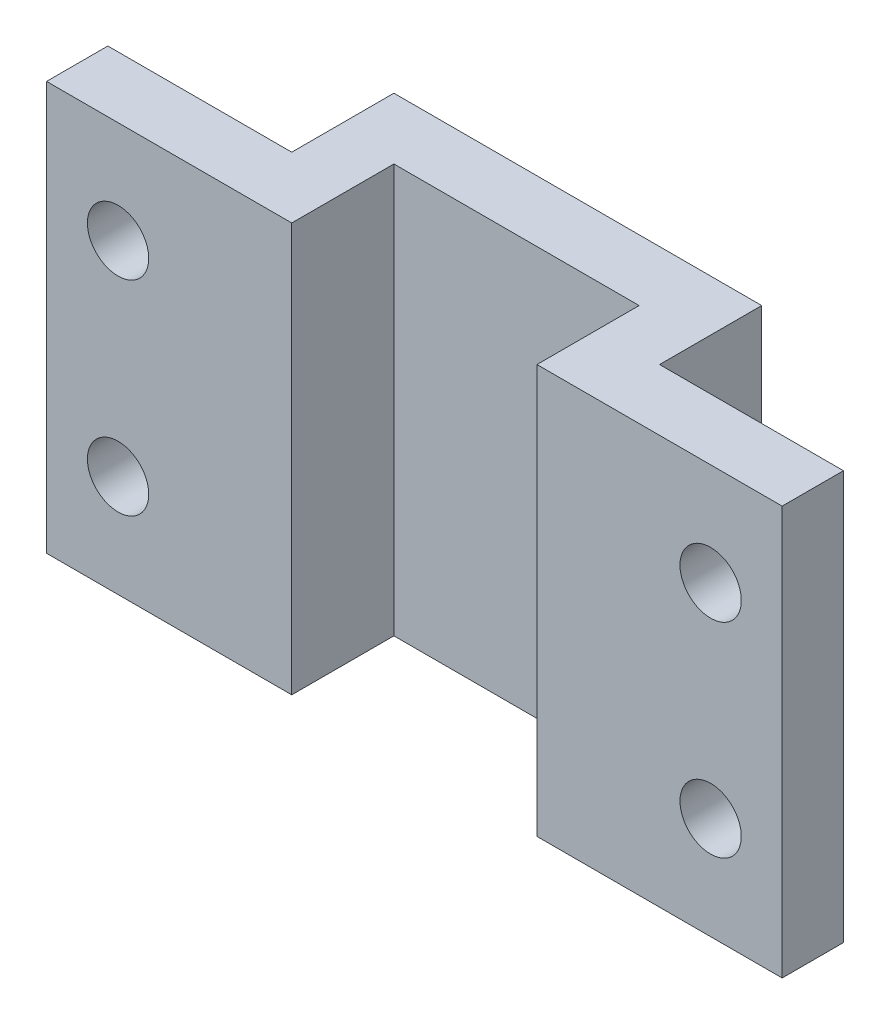
SolidWorks part; units mm, degrees
ref_plane "Front Plane" through (0, 0, 0) normal (0, 0, 1) x (1, 0, 0)
ref_plane "Top Plane" through (0, 0, 0) normal (0, 1, 0) x (1, 0, 0)
ref_plane "Right Plane" through (0, 0, 0) normal (1, 0, 0) x (0, 0, -1)
sketch "Sketch1" plane through (0, 0, 0) normal (0, 1, 0) x (1, 0, 0)
  line L0 (16.4704, -3) -> (28.4704, -3)
  line L1 (1.4704, 5) -> (19.4704, 5)
  line L2 (-7.5296, 0) -> (-7.5296, -3)
  line L3 (-7.5296, -3) -> (4.4704, -3)
  line L4 (28.4704, 0) -> (28.4704, -3)
  line L6 (4.4704, -3) -> (4.4704, 2)
  line L7 (4.4704, 2) -> (16.4704, 2)
  line L8 (16.4704, -3) -> (16.4704, 2)
  line L17 (1.4704, 5) -> (1.4704, 0)
  line L18 (1.4704, 0) -> (-7.5296, 0)
  line L19 (19.4704, 5) -> (19.4704, 0)
  line L20 (19.4704, 0) -> (28.4704, 0)
  dimension "D1" = 36
  dimension "D2" = 3
  dimension "D3" = 12
  dimension "D4" = 12
  dimension "D5" = 5
  dimension "D6" = 3
  dimension "D7" = 3
  dimension "D8" = 3
extrude "Boss-Extrude1" add sketch "Sketch1" along normal blind 20
sketch "Sketch2" plane through (0, 0, 0) normal (0, 0, -1) x (-1, 0, 0)
  line L0 (-1.4704, 20) -> (7.5296, 20) construction
  line L1 (7.5296, 20) -> (7.5296, 0) construction
  line L2 (-28.4704, 20) -> (-28.4704, 0) construction
  line L3 (-28.4704, 20) -> (-19.4704, 20) construction
  circle A0 centre (4.0296, 15) radius 1.5
  circle A1 centre (4.0296, 5) radius 1.5
  circle A2 centre (-24.9704, 5) radius 1.5
  circle A3 centre (-24.9704, 15) radius 1.5
  point P10 (-24.4089, 5)
  point P13 (-24.4089, 15)
  point P14 (0, 0)
  point P19 (0, 0)
  point P20 (0, 0)
  dimension "D5" = 3
  dimension "D6" = 3
  dimension "D1" = 5
  dimension "D2" = 3.5
  dimension "D3" = 3.5
  dimension "D4" = 10
  dimension "D7" = 3.5
  dimension "D8" = 3.5
  dimension "D9" = 5
  dimension "D10" = 10
extrude "Cut-Extrude1" cut sketch "Sketch2" against normal blind 16
